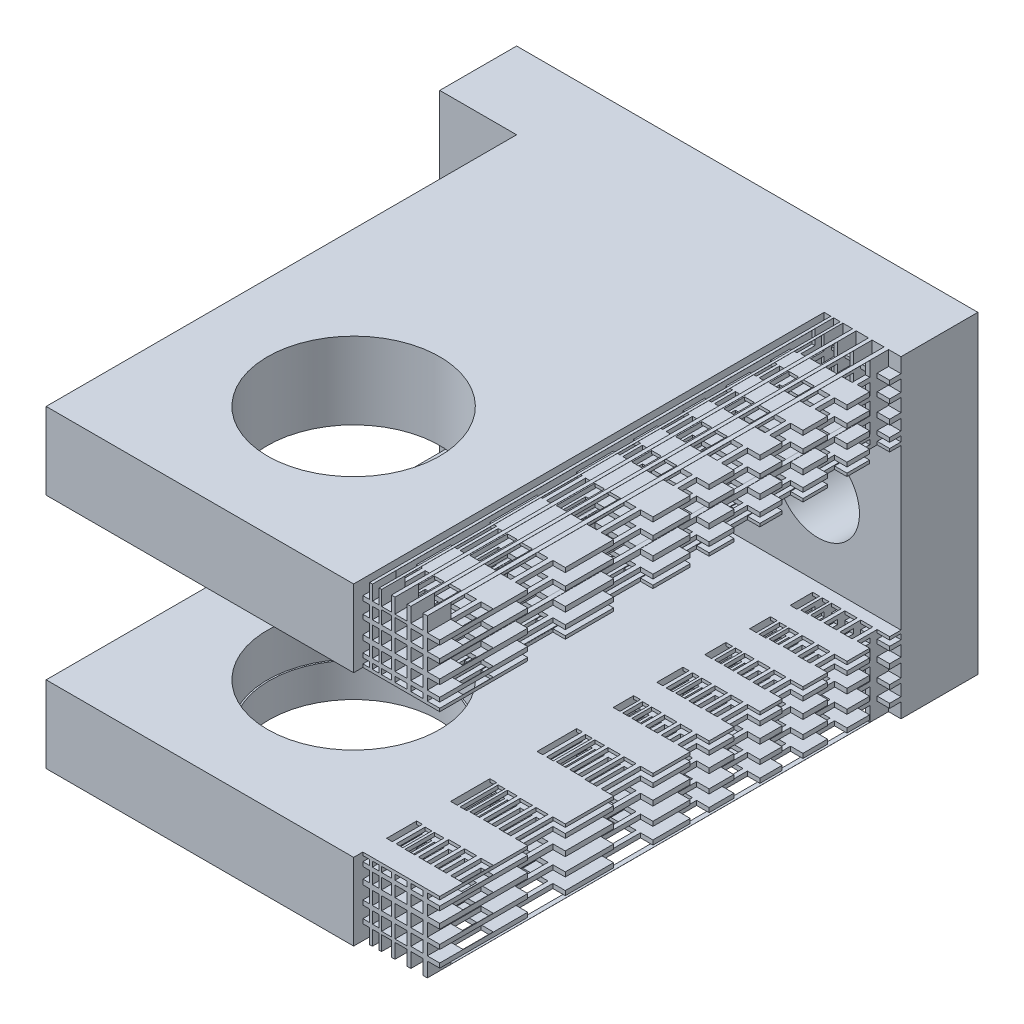
SolidWorks part; units mm, degrees
ref_plane "Front Plane" through (0, 0, 0) normal (0, 0, 1) x (1, 0, 0)
ref_plane "Top Plane" through (0, 0, 0) normal (0, 1, 0) x (1, 0, 0)
ref_plane "Right Plane" through (0, 0, 0) normal (1, 0, 0) x (0, 0, -1)
ref_plane "Plane1" through (0, 9.779, 0) normal (0, -1, 0) x (1, 0, 0)
sketch "Sketch1" plane through (0, 9.779, 0) normal (0, -1, 0) x (1, 0, 0)
  line L0 (-6.35, 11.303) -> (-6.35, -11.303)
  line L1 (-6.35, -11.303) -> (6.35, -11.303)
  line L2 (6.35, -11.303) -> (6.35, 11.303)
  line L3 (6.35, 11.303) -> (-6.35, 11.303)
  circle A0 centre (0, 4.953) radius 3.556
  dimension "D1" = 7.112
extrude "Boss-Extrude1" add sketch "Sketch1" against normal blind 3.175
sketch "Sketch2" plane through (-6.35, 0, 0) normal (-1, 0, 0) x (0, 0, 1)
  line L0 (-8.128, 9.779) -> (-11.303, 9.779)
  line L1 (-11.303, 9.779) -> (-11.303, 12.954)
  line L2 (-11.303, 12.954) -> (-8.128, 12.954)
  line L3 (-8.128, 12.954) -> (-8.128, 9.779)
extrude "Boss-Extrude2" add sketch "Sketch2" along normal blind 3.175
sketch "Sketch3" plane through (6.35, 0, 0) normal (1, 0, 0) x (0, 0, -1)
  line L0 (11.303, 9.779) -> (8.128, 9.779)
  line L1 (8.128, 9.779) -> (8.128, 12.954)
  line L2 (8.128, 12.954) -> (11.303, 12.954)
  line L3 (11.303, 12.954) -> (11.303, 9.779)
extrude "Boss-Extrude3" add sketch "Sketch3" along normal blind 3.175
sketch "Sketch4" plane through (0, 9.779, 0) normal (0, -1, 0) x (1, 0, 0)
  line L0 (-9.525, -8.128) -> (9.525, -8.128)
  line L1 (9.525, -8.128) -> (9.525, -11.303)
  line L2 (9.525, -11.303) -> (-9.525, -11.303)
  line L3 (-9.525, -11.303) -> (-9.525, -8.128)
extrude "Boss-Extrude4" add sketch "Sketch4" along normal blind 6.604
sketch "Sketch5" plane through (0, 3.175, 0) normal (0, -1, 0) x (1, 0, 0)
  line L0 (-6.35, 11.303) -> (6.35, 11.303)
  line L4 (6.35, 11.303) -> (6.35, -8.128)
  line L5 (6.35, -8.128) -> (9.525, -8.128)
  line L6 (9.525, -8.128) -> (9.525, -11.303)
  line L7 (9.525, -11.303) -> (-9.525, -11.303)
  line L8 (-9.525, -11.303) -> (-9.525, -8.128)
  line L9 (-9.525, -8.128) -> (-6.35, -8.128)
  line L10 (-6.35, -8.128) -> (-6.35, 11.303)
  circle A0 centre (0, 4.953) radius 3.556
  dimension "D1" = 7.112
extrude "Boss-Extrude5" add sketch "Sketch5" along normal blind 1.778
sketch "Sketch6" plane through (0, 1.397, 0) normal (0, -1, 0) x (1, 0, 0)
  line L0 (-9.525, -8.128) -> (-6.35, -8.128)
  line L1 (-6.35, -8.128) -> (-6.35, 11.303)
  line L2 (-6.35, 11.303) -> (6.35, 11.303)
  line L3 (6.35, 11.303) -> (6.35, -8.128)
  line L4 (6.35, -8.128) -> (9.525, -8.128)
  line L5 (9.525, -8.128) -> (9.525, -11.303)
  line L6 (9.525, -11.303) -> (-9.525, -11.303)
  line L7 (-9.525, -11.303) -> (-9.525, -8.128)
  circle A0 centre (0, 4.953) radius 3.4925
extrude "Boss-Extrude6" add sketch "Sketch6" along normal blind 1.397
hole_wizard "Hole1" positions "Sketch11" profile "Sketch10" legacy
sketch "Sketch11" plane through (0, 0, -11.303) normal (0, 0, -1) x (-1, 0, 0)
  point P0 (-6.096, 6.477)
sketch "Sketch10" plane through (6.096, 6.477, -11.303) normal (1, 0, 0) x (0, 1, 0)
  line L0 (0, 0) -> (0, 22.606)
  line L1 (0, 22.606) -> (1.7145, 22.606)
  line L2 (1.7145, 22.606) -> (1.7145, 0)
  line L3 (1.7145, 0) -> (0, 0)
  line L4 (0, 110) -> (0, -10) construction
  dimension "Diameter" = 3.429
  dimension "Depth" = 22.606
hole_wizard "Hole2" positions "Sketch13" profile "Sketch12" legacy
sketch "Sketch13" plane through (0, 0, -11.303) normal (0, 0, -1) x (-1, 0, 0)
  point P0 (6.096, 6.477)
sketch "Sketch12" plane through (-6.096, 6.477, -11.303) normal (1, 0, 0) x (0, 1, 0)
  line L0 (0, 0) -> (0, 22.606)
  line L1 (0, 22.606) -> (1.7145, 22.606)
  line L2 (1.7145, 22.606) -> (1.7145, 0)
  line L3 (1.7145, 0) -> (0, 0)
  line L4 (0, 110) -> (0, -10) construction
  dimension "Diameter" = 3.429
  dimension "Depth" = 22.606
sketch "Sketch16" plane through (0, 0, -8.128) normal (0, 0, 1) x (1, 0, 0)
  line L0 (6.6287, 12.954) -> (6.6287, 12.3458)
  line L1 (9.525, 12.954) -> (6.35, 12.954) construction
  line L2 (6.6287, 12.3458) -> (6.35, 12.3458)
  line L3 (6.35, 12.954) -> (6.35, 9.779) construction
  line L4 (6.35, 12.3458) -> (6.35, 12.1617)
  line L5 (6.35, 12.1617) -> (6.6287, 12.1617)
  line L6 (6.6287, 12.1617) -> (6.6287, 11.6782)
  line L7 (6.6287, 11.6782) -> (6.35, 11.6782)
  line L8 (6.35, 11.6782) -> (6.35, 11.494)
  line L9 (6.35, 11.494) -> (6.6287, 11.494)
  line L10 (6.6287, 11.494) -> (6.6287, 10.953)
  line L11 (6.6287, 10.953) -> (6.35, 10.953)
  line L12 (6.35, 12.954) -> (6.35, 9.779) construction
  line L13 (6.35, 10.953) -> (6.35, 10.7458)
  line L14 (6.35, 10.7458) -> (6.6287, 10.7458)
  line L15 (6.6287, 10.7458) -> (6.6287, 10.2969)
  line L16 (6.6287, 10.2969) -> (6.35, 10.2969)
  line L17 (6.35, 10.2969) -> (6.35, 10.1242)
  line L18 (6.35, 10.1242) -> (6.6287, 10.1242)
  line L19 (6.6287, 10.1242) -> (6.6287, 9.9055)
  line L20 (6.6287, 9.9055) -> (6.35, 9.9055)
  line L21 (6.35, 9.9055) -> (6.35, 9.779)
  line L22 (6.35, 9.779) -> (9.525, 9.779)
  line L23 (9.525, 12.954) -> (9.525, 0) construction
  line L24 (9.525, 9.779) -> (9.525, 9.9055)
  line L25 (9.525, 9.9055) -> (9.0114, 9.9055)
  line L26 (9.0114, 9.9055) -> (9.0114, 10.1242)
  line L27 (9.0114, 10.1242) -> (9.525, 10.1242)
  line L28 (9.525, 10.1242) -> (9.525, 10.2969)
  line L29 (9.525, 10.2969) -> (9.0114, 10.2969)
  line L30 (9.0114, 10.2969) -> (9.0114, 10.7458)
  line L31 (9.0114, 10.7458) -> (9.525, 10.7458)
  line L32 (9.525, 10.7458) -> (9.525, 10.953)
  line L33 (9.525, 10.953) -> (9.0114, 10.953)
  line L34 (9.0114, 10.953) -> (9.0114, 11.494)
  line L35 (9.0114, 11.494) -> (9.525, 11.494)
  line L36 (9.525, 11.494) -> (9.525, 11.6782)
  line L37 (9.525, 11.6782) -> (9.0114, 11.6782)
  line L38 (9.0114, 11.6782) -> (9.0114, 12.1617)
  line L39 (9.0114, 12.1617) -> (9.525, 12.1617)
  line L40 (9.525, 12.1617) -> (9.525, 12.3458)
  line L41 (9.525, 12.3458) -> (9.0114, 12.3458)
  line L42 (9.0114, 12.3458) -> (9.0114, 12.954)
  line L43 (9.0114, 12.954) -> (8.8273, 12.954)
  line L44 (8.8273, 12.954) -> (8.8273, 12.3458)
  line L45 (8.8273, 12.3458) -> (8.3323, 12.3458)
  line L46 (8.3323, 12.3458) -> (8.3323, 12.954)
  line L47 (8.3323, 12.954) -> (8.1826, 12.954)
  line L48 (8.1826, 12.954) -> (8.1826, 12.3458)
  line L49 (8.1826, 12.3458) -> (7.6762, 12.3458)
  line L50 (7.6762, 12.3458) -> (7.6762, 12.954)
  line L51 (7.6762, 12.954) -> (7.5265, 12.954)
  line L52 (7.5265, 12.954) -> (7.5265, 12.3458)
  line L53 (7.5265, 12.3458) -> (7.1236, 12.3458)
  line L54 (7.1236, 12.3458) -> (7.1236, 12.954)
  line L55 (7.1236, 12.954) -> (7.02, 12.954)
  line L56 (7.02, 12.954) -> (7.02, 12.3458)
  line L57 (7.02, 12.3458) -> (6.7438, 12.3458)
  line L58 (6.7438, 12.3458) -> (6.7438, 12.954)
  line L59 (6.7438, 12.954) -> (6.6287, 12.954)
  line L60 (8.8273, 12.1617) -> (8.3323, 12.1617)
  line L61 (8.3323, 12.1617) -> (8.3323, 11.6782)
  line L62 (8.3323, 11.6782) -> (8.8273, 11.6782)
  line L63 (8.8273, 11.6782) -> (8.8273, 12.1617)
  line L64 (8.8273, 11.494) -> (8.3323, 11.494)
  line L65 (8.3323, 11.494) -> (8.3323, 10.953)
  line L66 (8.3323, 10.953) -> (8.8273, 10.953)
  line L67 (8.8273, 10.953) -> (8.8273, 11.494)
  line L68 (8.8273, 10.7458) -> (8.8273, 10.2969)
  line L69 (8.8273, 10.2969) -> (8.3323, 10.2969)
  line L70 (8.3323, 10.2969) -> (8.3323, 10.7458)
  line L71 (8.3323, 10.7458) -> (8.8273, 10.7458)
  line L72 (8.8273, 10.1242) -> (8.3323, 10.1242)
  line L73 (8.3323, 10.1242) -> (8.3323, 9.9055)
  line L74 (8.3323, 9.9055) -> (8.8273, 9.9055)
  line L75 (8.8273, 9.9055) -> (8.8273, 10.1242)
  line L76 (7.6762, 12.2271) -> (8.1826, 12.2271)
  line L77 (8.1826, 12.2271) -> (8.1826, 11.6782)
  line L78 (8.1826, 11.6782) -> (7.6762, 11.6782)
  line L79 (7.6762, 11.6782) -> (7.6762, 12.2271)
  line L80 (7.6762, 11.494) -> (8.1826, 11.494)
  line L81 (8.1826, 11.494) -> (8.1826, 10.953)
  line L82 (8.1826, 10.953) -> (7.6762, 10.953)
  line L83 (7.6762, 10.953) -> (7.6762, 11.494)
  line L84 (7.6762, 10.7458) -> (8.1826, 10.7458)
  line L85 (8.1826, 10.7458) -> (8.1826, 10.2969)
  line L86 (8.1826, 10.2969) -> (7.6762, 10.2969)
  line L87 (7.6762, 10.2969) -> (7.6762, 10.7458)
  line L88 (7.6762, 10.1242) -> (7.6762, 9.9055)
  line L89 (7.6762, 9.9055) -> (8.1826, 9.9055)
  line L90 (8.1826, 9.9055) -> (8.1826, 10.1242)
  line L91 (8.1826, 10.1242) -> (7.6762, 10.1242)
  line L92 (7.1236, 12.2271) -> (7.5265, 12.2271)
  line L93 (7.5265, 12.2271) -> (7.5265, 11.6782)
  line L94 (7.5265, 11.6782) -> (7.1236, 11.6782)
  line L95 (7.1236, 11.6782) -> (7.1236, 12.2271)
  line L96 (7.1236, 11.494) -> (7.5265, 11.494)
  line L97 (7.5265, 11.494) -> (7.5265, 10.953)
  line L98 (7.5265, 10.953) -> (7.1236, 10.953)
  line L99 (7.1236, 10.953) -> (7.1236, 11.494)
  line L100 (7.5265, 10.7458) -> (7.1236, 10.7458)
  line L101 (7.1236, 10.7458) -> (7.1236, 10.2969)
  line L102 (7.1236, 10.2969) -> (7.5265, 10.2969)
  line L103 (7.5265, 10.2969) -> (7.5265, 10.7458)
  line L104 (7.5265, 10.1242) -> (7.1236, 10.1242)
  line L105 (7.1236, 10.1242) -> (7.1236, 9.9055)
  line L106 (7.1236, 9.9055) -> (7.5265, 9.9055)
  line L107 (7.5265, 9.9055) -> (7.5265, 10.1242)
  line L108 (6.7438, 12.1617) -> (7.02, 12.1617)
  line L109 (7.02, 12.1617) -> (7.02, 11.6782)
  line L110 (7.02, 11.6782) -> (6.7438, 11.6782)
  line L111 (6.7438, 11.6782) -> (6.7438, 12.1617)
  line L112 (6.7438, 11.494) -> (7.02, 11.494)
  line L113 (7.02, 11.494) -> (7.02, 10.953)
  line L114 (7.02, 10.953) -> (6.7438, 10.953)
  line L115 (6.7438, 10.953) -> (6.7438, 11.494)
  line L116 (6.7438, 10.7458) -> (7.02, 10.7458)
  line L117 (7.02, 10.7458) -> (7.02, 10.2969)
  line L118 (7.02, 10.2969) -> (6.7438, 10.2969)
  line L119 (6.7438, 10.2969) -> (6.7438, 10.7458)
  line L120 (6.7438, 10.1242) -> (6.7438, 9.9055)
  line L121 (6.7438, 9.9055) -> (7.02, 9.9055)
  line L122 (7.02, 9.9055) -> (7.02, 10.1242)
  line L123 (7.02, 10.1242) -> (6.7438, 10.1242)
extrude "Boss-Extrude8" add sketch "Sketch16" along normal blind 19.05
sketch "Sketch17" plane through (0, 12.954, 0) normal (0, 1, 0) x (1, 0, 0)
  line L0 (6.35, 7.6583) -> (6.6287, 7.6583)
  line L1 (6.35, 7.6583) -> (6.35, 6.7258)
  line L2 (6.6287, 7.6583) -> (6.6287, 6.7258)
  line L3 (6.35, 6.7258) -> (6.6287, 6.7258)
  line L4 (6.35, -10.922) -> (6.35, 8.128) construction
  line L5 (6.6287, -10.922) -> (6.6287, 8.128) construction
  line L6 (6.7438, 7.6583) -> (7.02, 7.6583)
  line L7 (6.7438, 7.6583) -> (6.7438, 6.7759)
  line L8 (7.02, 7.6583) -> (7.02, 6.7759)
  line L9 (6.7438, 6.7759) -> (7.02, 6.7759)
  line L12 (6.7438, -10.922) -> (6.7438, 8.128) construction
  line L13 (7.02, -10.922) -> (7.02, 8.128) construction
  line L14 (7.1236, 7.6583) -> (7.5265, 7.6583)
  line L15 (7.1236, 7.6583) -> (7.1236, 6.796)
  line L16 (7.5265, 7.6583) -> (7.5265, 6.796)
  line L17 (7.1236, 6.796) -> (7.5265, 6.796)
  line L20 (7.1236, -10.922) -> (7.1236, 8.128) construction
  line L21 (7.5265, -10.922) -> (7.5265, 8.128) construction
  line L22 (7.6762, 7.6583) -> (8.1826, 7.6583)
  line L23 (7.6762, 7.6583) -> (7.6762, 6.8021)
  line L24 (8.1826, 7.6583) -> (8.1826, 6.8021)
  line L25 (7.6762, 6.8021) -> (8.1826, 6.8021)
  line L28 (7.6762, -10.922) -> (7.6762, 8.128) construction
  line L29 (8.1826, -10.922) -> (8.1826, 8.128) construction
  line L30 (8.3323, 7.6583) -> (8.8273, 7.6583)
  line L31 (8.3323, 7.6583) -> (8.3323, 6.8054)
  line L32 (8.8273, 7.6583) -> (8.8273, 6.8054)
  line L33 (8.3323, 6.8054) -> (8.8273, 6.8054)
  line L36 (8.3323, -10.922) -> (8.3323, 8.128) construction
  line L37 (8.8273, -10.922) -> (8.8273, 8.128) construction
  line L38 (9.0114, 7.6583) -> (9.525, 7.6583)
  line L39 (9.0114, 7.6583) -> (9.0114, 6.8311)
  line L40 (9.525, 7.6583) -> (9.525, 6.8311)
  line L41 (9.0114, 6.8311) -> (9.525, 6.8311)
  line L44 (9.0114, -10.922) -> (9.0114, 8.128) construction
  line L45 (9.525, -10.922) -> (9.525, 8.128) construction
  line L46 (6.35, 5.9138) -> (6.6287, 5.9138)
  line L47 (6.35, 5.9138) -> (6.35, 5.0512)
  line L48 (6.6287, 5.9138) -> (6.6287, 5.0512)
  line L49 (6.35, 5.0512) -> (6.6287, 5.0512)
  line L50 (6.35, 8.128) -> (6.35, -11.303) construction
  line L51 (6.7438, 5.0512) -> (7.02, 5.0512)
  line L52 (6.7438, 5.0512) -> (6.7438, 5.8969)
  line L53 (7.02, 5.0512) -> (7.02, 5.8969)
  line L54 (6.7438, 5.8969) -> (7.02, 5.8969)
  line L57 (6.7438, -10.922) -> (6.7438, 8.128) construction
  line L58 (7.02, -10.922) -> (7.02, 8.128) construction
  line L59 (7.1236, 5.8969) -> (7.5265, 5.8969)
  line L60 (7.1236, 5.8969) -> (7.1236, 5.085)
  line L61 (7.5265, 5.8969) -> (7.5265, 5.085)
  line L62 (7.1236, 5.085) -> (7.5265, 5.085)
  line L64 (7.1236, -10.922) -> (7.1236, 8.128) construction
  line L65 (7.6762, 5.8969) -> (8.1826, 5.8969)
  line L66 (7.6762, 5.8969) -> (7.6762, 5.1104)
  line L67 (8.1826, 5.8969) -> (8.1826, 5.1104)
  line L68 (7.6762, 5.1104) -> (8.1826, 5.1104)
  line L70 (8.1826, -10.922) -> (8.1826, 8.128) construction
  line L71 (8.3323, 5.8969) -> (8.8273, 5.8969)
  line L72 (8.3323, 5.8969) -> (8.3323, 5.0681)
  line L73 (8.8273, 5.8969) -> (8.8273, 5.0681)
  line L74 (8.3323, 5.0681) -> (8.8273, 5.0681)
  line L76 (8.3323, -10.922) -> (8.3323, 8.128) construction
  line L77 (9.0114, 5.8969) -> (9.525, 5.8969)
  line L78 (9.0114, 5.8969) -> (9.0114, 5.0935)
  line L79 (9.525, 5.8969) -> (9.525, 5.0935)
  line L80 (9.0114, 5.0935) -> (9.525, 5.0935)
  line L82 (9.0114, -10.922) -> (9.0114, 8.128) construction
  line L83 (6.35, 4.0702) -> (6.6287, 4.0702)
  line L84 (6.35, 4.0702) -> (6.35, 3.1992)
  line L85 (6.6287, 4.0702) -> (6.6287, 3.1992)
  line L86 (6.35, 3.1992) -> (6.6287, 3.1992)
  line L87 (6.7438, 4.0702) -> (7.02, 4.0702)
  line L88 (6.7438, 4.0702) -> (6.7438, 3.2076)
  line L89 (7.02, 4.0702) -> (7.02, 3.2076)
  line L90 (6.7438, 3.2076) -> (7.02, 3.2076)
  line L91 (7.1236, 4.0702) -> (7.5265, 4.0702)
  line L92 (7.1236, 4.0702) -> (7.1236, 3.2096)
  line L93 (7.5265, 4.0702) -> (7.5265, 3.2096)
  line L94 (7.1236, 3.2096) -> (7.5265, 3.2096)
  line L95 (7.6762, 3.2096) -> (8.1826, 3.2096)
  line L96 (7.6762, 3.2096) -> (7.6762, 4.0784)
  line L97 (8.1826, 3.2096) -> (8.1826, 4.0784)
  line L98 (7.6762, 4.0784) -> (8.1826, 4.0784)
  line L99 (8.3323, 4.0784) -> (8.8273, 4.0784)
  line L100 (8.3323, 4.0784) -> (8.3323, 3.2064)
  line L101 (8.8273, 4.0784) -> (8.8273, 3.2064)
  line L102 (8.3323, 3.2064) -> (8.8273, 3.2064)
  line L104 (8.8273, -10.922) -> (8.8273, 8.128) construction
  line L105 (9.0114, 4.0784) -> (9.525, 4.0784)
  line L106 (9.0114, 4.0784) -> (9.0114, 3.2206)
  line L107 (9.525, 4.0784) -> (9.525, 3.2206)
  line L108 (9.0114, 3.2206) -> (9.525, 3.2206)
  line L110 (9.525, -10.922) -> (9.525, 8.128) construction
  line L111 (6.35, 2.3005) -> (6.35, 1.2182)
  line L112 (6.35, 2.3005) -> (6.6002, 2.3005)
  line L113 (6.35, 1.2182) -> (6.6002, 1.2182)
  line L114 (6.6002, 2.3005) -> (6.6002, 1.2182)
  line L115 (6.7438, 2.3005) -> (7.02, 2.3005)
  line L116 (6.7438, 2.3005) -> (6.7438, 1.2103)
  line L117 (7.02, 2.3005) -> (7.02, 1.2103)
  line L118 (6.7438, 1.2103) -> (7.02, 1.2103)
  line L119 (7.1236, 2.3005) -> (7.5265, 2.3005)
  line L120 (7.1236, 2.3005) -> (7.1236, 1.2232)
  line L121 (7.5265, 2.3005) -> (7.5265, 1.2232)
  line L122 (7.1236, 1.2232) -> (7.5265, 1.2232)
  line L123 (7.6762, 2.3005) -> (8.1826, 2.3005)
  line L124 (7.6762, 2.3005) -> (7.6762, 1.2137)
  line L125 (8.1826, 2.3005) -> (8.1826, 1.2137)
  line L126 (7.6762, 1.2137) -> (8.1826, 1.2137)
  line L127 (8.3323, 2.3005) -> (8.8273, 2.3005)
  line L128 (8.3323, 2.3005) -> (8.3323, 1.232)
  line L129 (8.8273, 2.3005) -> (8.8273, 1.232)
  line L130 (8.3323, 1.232) -> (8.8273, 1.232)
  line L131 (9.0114, 2.3005) -> (9.525, 2.3005)
  line L132 (9.0114, 2.3005) -> (9.0114, 1.2256)
  line L133 (9.525, 2.3005) -> (9.525, 1.2256)
  line L134 (9.0114, 1.2256) -> (9.525, 1.2256)
  line L135 (6.35, 0.2623) -> (6.6287, 0.2623)
  line L136 (6.35, 0.2623) -> (6.35, -0.5815)
  line L137 (6.6287, 0.2623) -> (6.6287, -0.5815)
  line L138 (6.35, -0.5815) -> (6.6287, -0.5815)
  line L139 (6.7438, -0.5815) -> (7.02, -0.5815)
  line L140 (6.7438, -0.5815) -> (6.7438, 0.2315)
  line L141 (7.02, -0.5815) -> (7.02, 0.2315)
  line L142 (6.7438, 0.2315) -> (7.02, 0.2315)
  line L143 (7.1236, 0.2315) -> (7.5265, 0.2315)
  line L144 (7.1236, 0.2315) -> (7.1236, -0.5866)
  line L145 (7.5265, 0.2315) -> (7.5265, -0.5866)
  line L146 (7.1236, -0.5866) -> (7.5265, -0.5866)
  line L147 (7.6762, -0.5866) -> (8.1826, -0.5866)
  line L148 (7.6762, -0.5866) -> (7.6762, 0.216)
  line L149 (8.1826, -0.5866) -> (8.1826, 0.216)
  line L150 (7.6762, 0.216) -> (8.1826, 0.216)
  line L151 (8.3323, 0.216) -> (8.8273, 0.216)
  line L152 (8.3323, 0.216) -> (8.3323, -0.5763)
  line L153 (8.8273, 0.216) -> (8.8273, -0.5763)
  line L154 (8.3323, -0.5763) -> (8.8273, -0.5763)
  line L155 (9.0114, -0.5763) -> (9.525, -0.5763)
  line L156 (9.0114, -0.5763) -> (9.0114, 0.201)
  line L157 (9.525, -0.5763) -> (9.525, 0.201)
  line L158 (9.0114, 0.201) -> (9.525, 0.201)
  line L159 (6.35, -2.0923) -> (6.35, -3.729)
  line L160 (6.35, -2.0923) -> (6.5837, -2.0923)
  line L161 (6.35, -3.729) -> (6.5837, -3.729)
  line L162 (6.5837, -2.0923) -> (6.5837, -3.729)
  line L163 (6.7438, -3.729) -> (7.02, -3.729)
  line L164 (6.7438, -3.729) -> (6.7438, -2.1171)
  line L165 (7.02, -3.729) -> (7.02, -2.1171)
  line L166 (6.7438, -2.1171) -> (7.02, -2.1171)
  line L167 (7.1236, -2.1171) -> (7.5265, -2.1171)
  line L168 (7.1236, -2.1171) -> (7.1236, -3.7042)
  line L169 (7.5265, -2.1171) -> (7.5265, -3.7042)
  line L170 (7.1236, -3.7042) -> (7.5265, -3.7042)
  line L171 (7.6762, -3.7042) -> (8.1826, -3.7042)
  line L172 (7.6762, -3.7042) -> (7.6762, -2.1171)
  line L173 (8.1826, -3.7042) -> (8.1826, -2.1171)
  line L174 (7.6762, -2.1171) -> (8.1826, -2.1171)
  line L175 (8.3323, -2.1171) -> (8.8273, -2.1171)
  line L176 (8.3323, -2.1171) -> (8.3323, -3.7414)
  line L177 (8.8273, -2.1171) -> (8.8273, -3.7414)
  line L178 (8.3323, -3.7414) -> (8.8273, -3.7414)
  line L179 (9.0114, -3.7414) -> (9.525, -3.7414)
  line L180 (9.0114, -3.7414) -> (9.0114, -2.1171)
  line L181 (9.525, -3.7414) -> (9.525, -2.1171)
  line L182 (9.0114, -2.1171) -> (9.525, -2.1171)
  line L183 (9.525, -5.7376) -> (9.525, -7.2874)
  line L184 (9.525, -5.7376) -> (9.0139, -5.7376)
  line L185 (9.525, -7.2874) -> (9.0139, -7.2874)
  line L186 (9.0139, -5.7376) -> (9.0139, -7.2874)
  line L187 (8.8273, -7.2874) -> (8.3323, -7.2874)
  line L188 (8.8273, -7.2874) -> (8.8273, -5.75)
  line L189 (8.3323, -7.2874) -> (8.3323, -5.75)
  line L190 (8.8273, -5.75) -> (8.3323, -5.75)
  line L191 (8.1826, -5.75) -> (7.6762, -5.75)
  line L192 (8.1826, -5.75) -> (8.1826, -7.275)
  line L193 (7.6762, -5.75) -> (7.6762, -7.275)
  line L194 (8.1826, -7.275) -> (7.6762, -7.275)
  line L195 (7.5265, -7.275) -> (7.1236, -7.275)
  line L196 (7.5265, -7.275) -> (7.5265, -5.7252)
  line L197 (7.1236, -7.275) -> (7.1236, -5.7252)
  line L198 (7.5265, -5.7252) -> (7.1236, -5.7252)
  line L199 (7.02, -5.7252) -> (6.7438, -5.7252)
  line L200 (7.02, -5.7252) -> (7.02, -7.2998)
  line L201 (6.7438, -5.7252) -> (6.7438, -7.2998)
  line L202 (7.02, -7.2998) -> (6.7438, -7.2998)
  line L203 (6.6287, -7.2998) -> (6.35, -7.2998)
  line L204 (6.6287, -7.2998) -> (6.6287, -5.6756)
  line L205 (6.35, -7.2998) -> (6.35, -5.6756)
  line L206 (6.6287, -5.6756) -> (6.35, -5.6756)
  line L207 (6.35, -8.7025) -> (6.35, -9.9432)
  line L208 (6.35, -8.7025) -> (6.5893, -8.7025)
  line L209 (6.35, -9.9432) -> (6.5893, -9.9432)
  line L210 (6.5893, -8.7025) -> (6.5893, -9.9432)
  line L211 (6.7438, -9.9432) -> (7.02, -9.9432)
  line L212 (6.7438, -9.9432) -> (6.7438, -8.7428)
  line L213 (7.02, -9.9432) -> (7.02, -8.7428)
  line L214 (6.7438, -8.7428) -> (7.02, -8.7428)
  line L215 (7.1236, -8.7428) -> (7.5265, -8.7428)
  line L216 (7.1236, -8.7428) -> (7.1236, -9.9533)
  line L217 (7.5265, -8.7428) -> (7.5265, -9.9533)
  line L218 (7.1236, -9.9533) -> (7.5265, -9.9533)
  line L220 (7.5265, -10.922) -> (7.5265, 8.128) construction
  line L221 (7.6762, -9.9533) -> (8.1826, -9.9533)
  line L222 (7.6762, -9.9533) -> (7.6762, -8.7025)
  line L223 (8.1826, -9.9533) -> (8.1826, -8.7025)
  line L224 (7.6762, -8.7025) -> (8.1826, -8.7025)
  line L226 (7.6762, -10.922) -> (7.6762, 8.128) construction
  line L227 (8.3323, -8.7025) -> (8.8273, -8.7025)
  line L228 (8.3323, -8.7025) -> (8.3323, -9.9533)
  line L229 (8.8273, -8.7025) -> (8.8273, -9.9533)
  line L230 (8.3323, -9.9533) -> (8.8273, -9.9533)
  line L231 (9.0114, -8.7025) -> (9.0114, -9.9533)
  line L232 (9.0114, -8.7025) -> (9.5145, -8.7025)
  line L233 (9.0114, -9.9533) -> (9.5145, -9.9533)
  line L234 (9.5145, -8.7025) -> (9.5145, -9.9533)
extrude "Cut-Extrude2" cut sketch "Sketch17" against normal blind 3.81
sketch "Sketch18" plane through (9.0114, 0, 0) normal (1, 0, 0) x (0, 0, -1)
  line L0 (-9.9533, 12.3458) -> (-8.9011, 12.3458)
  line L1 (-9.9533, 12.3458) -> (-9.9533, 12.9497)
  line L2 (-8.9011, 12.3458) -> (-8.9011, 12.9497)
  line L3 (-9.9533, 12.9497) -> (-8.9011, 12.9497)
  line L4 (-10.922, 12.3458) -> (-7.2874, 12.3458) construction
  line L6 (-9.9533, 12.1617) -> (-9.9533, 11.6782)
  line L7 (-9.9533, 12.1617) -> (-8.9, 12.1617)
  line L8 (-9.9533, 11.6782) -> (-8.9, 11.6782)
  line L9 (-8.9, 12.1617) -> (-8.9, 11.6782)
  line L11 (-10.922, 12.1617) -> (-7.2874, 12.1617) construction
  line L12 (-8.9, 11.494) -> (-8.9, 10.9614)
  line L13 (-8.9, 11.494) -> (-9.9586, 11.494)
  line L14 (-8.9, 10.9614) -> (-9.9586, 10.9614)
  line L15 (-9.9586, 11.494) -> (-9.9586, 10.9614)
  line L16 (-10.922, 11.494) -> (-7.2874, 11.494) construction
  line L17 (-9.9533, 10.7458) -> (-9.9533, 10.2969)
  line L18 (-9.9533, 10.7458) -> (-8.9, 10.7458)
  line L19 (-9.9533, 10.2969) -> (-8.9, 10.2969)
  line L20 (-8.9, 10.7458) -> (-8.9, 10.2969)
  line L21 (-8.9, 10.1242) -> (-8.9, 9.9354)
  line L22 (-8.9, 10.1242) -> (-9.9717, 10.1242)
  line L23 (-8.9, 9.9354) -> (-9.9717, 9.9354)
  line L24 (-9.9717, 10.1242) -> (-9.9717, 9.9354)
  line L25 (-10.922, 10.1242) -> (-7.2874, 10.1242) construction
extrude "Cut-Extrude3" cut sketch "Sketch18" against normal blind 2.413
pattern_linear "LPattern4" count 17 spacing 1.016 along (0, 0, -1) of "Cut-Extrude3"
ref_plane "Plane2" through (0, 6.477, 0) normal (0, -1, 0) x (1, 0, 0)
mirror "Mirror1" about plane through (0, 6.477, 0) normal (0, -1, 0) of "Boss-Extrude8", "Cut-Extrude2", "Cut-Extrude3", "LPattern4"
